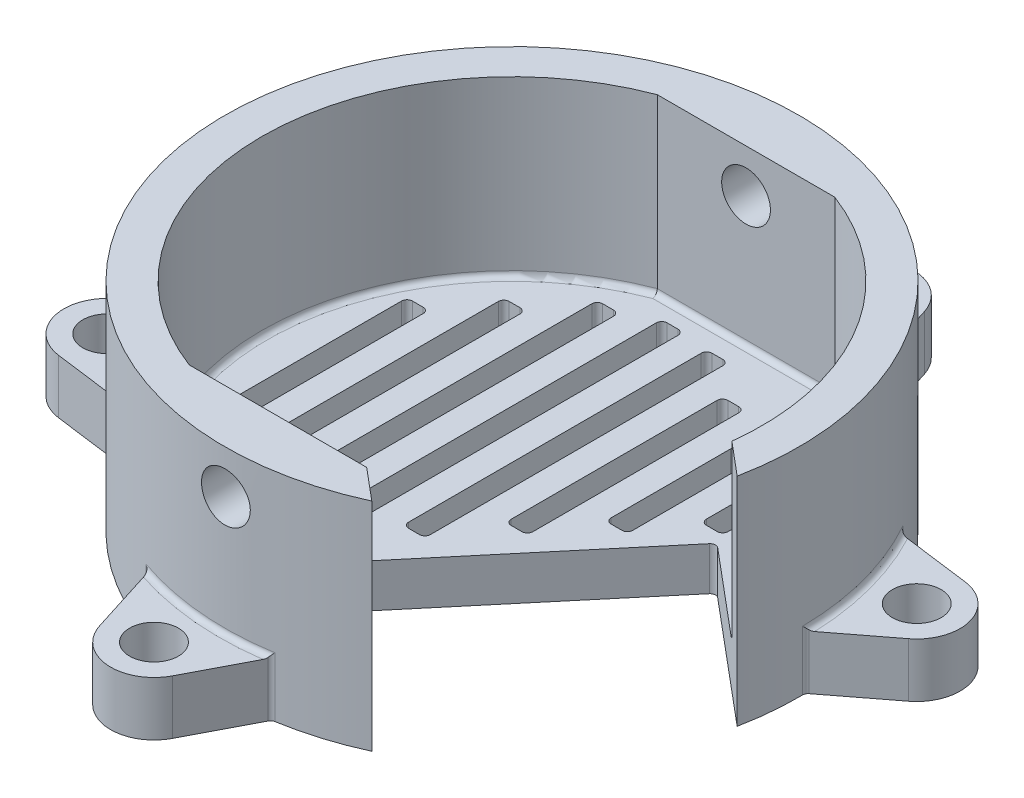
SolidWorks part; units mm, degrees
ref_plane "Front" through (0, 0, 0) normal (0, 0, 1) x (1, 0, 0)
ref_plane "Top" through (0, 0, 0) normal (0, 1, 0) x (1, 0, 0)
ref_plane "Right" through (0, 0, 0) normal (1, 0, 0) x (0, 0, -1)
sketch "Sketch1" plane through (0, 0, 0) normal (0, 1, 0) x (1, 0, 0)
  line L0 (-4.0942, 10.8) -> (4.0942, 10.8)
  line L1 (-4.0942, -10.8) -> (4.0942, -10.8)
  arc A0 (-4.0942, 10.8) -> (-4.0942, -10.8) centre (0, 0) ccw
  arc A1 (4.0942, -10.8) -> (4.0942, 10.8) centre (0, 0) ccw
  dimension "D1" = 23.1
  dimension "D2" = 10.8
  dimension "D3" = 10.8
extrude "Boss-Extrude1" add sketch "Sketch1" along normal blind 2
sketch "Sketch2" plane through (0, 0, 0) normal (0, 1, 0) x (1, 0, 0)
  line L2 (-4.0942, -10.8) -> (4.0942, -10.8)
  line L3 (4.0942, 10.8) -> (-4.0942, 10.8)
  line L4 (-4.0942, -10.8) -> (4.0942, -10.8)
  line L5 (4.0942, 10.8) -> (-4.0942, 10.8)
  circle A0 centre (0, 0) radius 13.25
  arc A3 (-4.0942, 10.8) -> (-4.0942, -10.8) centre (0, 0) ccw
  arc A4 (4.0942, -10.8) -> (4.0942, 10.8) centre (0, 0) ccw
  arc A5 (-4.0942, 10.8) -> (-4.0942, -10.8) centre (0, 0) ccw
  arc A6 (4.0942, -10.8) -> (4.0942, 10.8) centre (0, 0) ccw
  dimension "D1" = 26.5
  dimension "D2" = 0
extrude "Boss-Extrude2" add sketch "Sketch2" along normal blind 10
sketch "Sketch3" plane through (0, 2, 0) normal (0, 1, 0) x (1, 0, 0)
  line L0 (4.0942, -10.8) -> (-0.5021, -6.9433)
  line L1 (-0.5021, -6.9433) -> (7.2114, 2.2493)
  line L2 (7.2114, 2.2493) -> (11.4735, -1.3271)
  line L3 (4.4355, -12.6825) -> (13.8662, -1.4435) construction
  line L4 (3.3547, -2.347) -> (9.0782, -7.1496) construction
  line L5 (-4.0942, -10.8) -> (4.0942, -10.8) construction
  line L6 (4.0942, -10.8) -> (5.5577, -12.0281)
  line L7 (11.4735, -1.3271) -> (12.9921, -2.6014)
  arc A0 (4.0942, -10.8) -> (4.0942, 10.8) centre (0, 0) ccw construction
  circle A1 centre (0, 0) radius 13.25 construction
  arc A2 (12.9921, -2.6014) -> (5.5577, -12.0281) centre (0, 0) cw
  dimension "D1" = 12
  dimension "D2" = 40
  dimension "D3" = 6
extrude "Cut-Extrude1" cut sketch "Sketch3" along normal up to surface (8 mm away) up to face at (0, 10, 13.25)
extrude "Cut-Extrude3" cut sketch "Sketch3<3>" against normal up to surface (2 mm away) up to face at (0, 0, 13.25)
sketch "Sketch3<3>" plane through (0, 2, 0) normal (0, 1, 0) x (1, 0, 0) same geometry as "Sketch3"
sketch "Sketch4" plane through (0, 0, 0) normal (0, 0, 1) x (1, 0, 0)
  line L0 (0, 0) -> (0, 10) construction
  line L1 (-4.0942, 10) -> (4.0942, 10) construction
  circle A1 centre (0, 8) radius 1.125
  dimension "D1" = 2.25
  dimension "D2" = 2
extrude "Cut-Extrude4" cut sketch "Sketch4" against normal mid plane 30
sketch "Sketch5" plane through (0, 0, 0) normal (0, -1, 0) x (1, 0, 0)
  line L0 (0, 0) -> (1.1548, -13.1996) construction
  line L1 (0, 0) -> (0, -13.25) construction
  line L2 (3.2366, -15.7934) -> (4.2603, -12.5464)
  line L3 (-0.4449, -16.1155) -> (-2.0169, -13.0956)
  line L4 (0, 0) -> (11.4877, -13.6905) construction
  line L5 (-0.5021, 6.9433) -> (7.2114, -2.2493) construction
  line L6 (0, 0) -> (10.0176, 8.4058) construction
  line L7 (15.9479, -2.3603) -> (13.2469, -0.2877)
  line L8 (14.9914, -5.9299) -> (11.616, -6.3743)
  line L9 (-3.2366, 15.7934) -> (-4.2603, 12.5464)
  line L10 (0.4449, 16.1155) -> (2.0169, 13.0956)
  line L11 (-15.9479, 2.3603) -> (-13.2469, 0.2877)
  line L12 (-14.9914, 5.9299) -> (-11.616, 6.3743)
  arc A0 (5.5577, 12.0281) -> (12.9921, 2.6014) centre (0, 0) ccw construction
  circle A1 centre (1.3291, -15.192) radius 2 construction
  arc A2 (-0.4449, -16.1155) -> (3.2366, -15.7934) centre (1.3291, -15.192) ccw
  arc A3 (-2.0169, -13.0956) -> (4.2603, -12.5464) centre (0, 0) ccw
  arc A4 (5.5577, 12.0281) -> (12.9921, 2.6014) centre (0, 0) ccw construction
  circle A5 centre (1.3291, -15.192) radius 1.125
  circle A6 centre (14.7304, -3.947) radius 1.125
  arc A7 (15.9479, -2.3603) -> (14.9914, -5.9299) centre (14.7304, -3.947) cw
  arc A8 (13.2469, -0.2877) -> (11.616, -6.3743) centre (0, 0) cw
  arc A9 (0.4449, 16.1155) -> (-3.2366, 15.7934) centre (-1.3291, 15.192) ccw
  arc A10 (2.0169, 13.0956) -> (-4.2603, 12.5464) centre (0, 0) ccw
  circle A11 centre (-1.3291, 15.192) radius 1.125
  circle A12 centre (-14.7304, 3.947) radius 1.125
  arc A13 (-15.9479, 2.3603) -> (-14.9914, 5.9299) centre (-14.7304, 3.947) cw
  arc A14 (-13.2469, 0.2877) -> (-11.616, 6.3743) centre (0, 0) cw
  dimension "D2" = 4
  dimension "D3" = 45
  dimension "D4" = 2.25
  dimension "D1" = 5
extrude "Boss-Extrude4" add sketch "Sketch5" against normal blind 2.5
fillet "Fillet2" radius 0.25 18 edges at (-0.5021, 1, 6.9433) (7.2114, 1, -2.2493) (0, 2, 10.8) (9.8669, 2, -6.004) (-11.55, 2, 0) (0, 2, -10.8) (-1.1548, 2.5, 13.1996) (12.7985, 2.5, -3.4294) (1.1548, 2.5, -13.1996) (-12.7985, 2.5, 3.4294) (-2.0169, 1.25, -13.0956) (4.2603, 1.25, -12.5464) (11.616, 1.25, -6.3743) (13.2469, 1.25, -0.2877) (2.0169, 1.25, 13.0956) (-4.2603, 1.25, 12.5464) (-11.616, 1.25, 6.3743) (-13.2469, 1.25, 0.2877)
sketch "Sketch6" plane through (0, 0, 0) normal (0, -1, 0) x (1, 0, 0)
  line L1 (-9.75, 4.0968) -> (-8.75, 4.0968)
  line L2 (-9.75, 4.0968) -> (-9.75, -4.9032)
  line L3 (-9.75, -4.9032) -> (-8.75, -4.9032)
  line L4 (-8.75, 4.0968) -> (-8.75, -4.9032)
  line L5 (-7.5, 6.8805) -> (-6.5, 6.8805)
  line L6 (-7.5, 6.8805) -> (-7.5, -7.1195)
  line L7 (-7.5, -7.1195) -> (-6.5, -7.1195)
  line L8 (-6.5, 6.8805) -> (-6.5, -7.1195)
  line L9 (-5.25, 8.816) -> (-4.25, 8.816)
  line L10 (-5.25, 8.816) -> (-5.25, -9.184)
  line L11 (-5.25, -9.184) -> (-4.25, -9.184)
  line L12 (-4.25, 8.816) -> (-4.25, -9.184)
  line L13 (-3, 9.0929) -> (-2, 9.0929)
  line L14 (-3, 9.0929) -> (-3, -9.9071)
  line L15 (-3, -9.9071) -> (-2, -9.9071)
  line L16 (-2, 9.0929) -> (-2, -9.9071)
  line L17 (-0.75, 4.2695) -> (0.25, 4.2695)
  line L18 (-0.75, 4.2695) -> (-0.75, -9.7305)
  line L19 (-0.75, -9.7305) -> (0.25, -9.7305)
  line L20 (0.25, 4.2695) -> (0.25, -9.7305)
  line L21 (1.5, 1.7875) -> (2.5, 1.7875)
  line L22 (1.5, 1.7875) -> (1.5, -8.2125)
  line L23 (1.5, -8.2125) -> (2.5, -8.2125)
  line L24 (2.5, 1.7875) -> (2.5, -8.2125)
  line L25 (3.75, -0.573) -> (4.75, -0.573)
  line L26 (3.75, -0.573) -> (3.75, -6.573)
  line L27 (3.75, -6.573) -> (4.75, -6.573)
  line L28 (4.75, -0.573) -> (4.75, -6.573)
  line L29 (6, -2.7229) -> (7, -2.7229)
  line L30 (6, -2.7229) -> (6, -5.7229)
  line L31 (6, -5.7229) -> (7, -5.7229)
  line L32 (7, -2.7229) -> (7, -5.7229)
  dimension "D1" = 1
  dimension "D2" = 1.25
  dimension "D3" = 1.25
  dimension "D4" = 1.25
  dimension "D5" = 1.25
  dimension "D6" = 1.25
  dimension "D7" = 1.25
  dimension "D8" = 1.25
  dimension "D9" = 9
  dimension "D10" = 14
  dimension "D11" = 18
  dimension "D12" = 19
  dimension "D13" = 14
  dimension "D14" = 10
  dimension "D15" = 6
  dimension "D16" = 3
  dimension "D17" = 0.25
extrude "Cut-Extrude5" cut sketch "Sketch6" against normal up to surface (2 mm away) up to face at (2.1598, 2, 1.0622)
fillet "Fillet3" radius 0.25 32 edges at (-8.75, 1, 4.0968) (-6.5, 1, 6.8805) (-4.25, 1, 8.816) (-2, 1, 9.0929) (0.25, 1, 4.2695) (2.5, 1, 1.7875) (4.75, 1, -0.573) (7, 1, -2.7229) (-9.75, 1, 4.0968) (-7.5, 1, 6.8805) (-5.25, 1, 8.816) (-3, 1, 9.0929) (-0.75, 1, 4.2695) (1.5, 1, 1.7875) (3.75, 1, -0.573) (6, 1, -2.7229) (-6.5, 1, -7.1195) (-4.25, 1, -9.184) (-2, 1, -9.9071) (0.25, 1, -9.7305) (2.5, 1, -8.2125) (4.75, 1, -6.573) (7, 1, -5.7229) (-5.25, 1, -9.184) (-3, 1, -9.9071) (-0.75, 1, -9.7305) (1.5, 1, -8.2125) (3.75, 1, -6.573) (6, 1, -5.7229) (-7.5, 1, -7.1195) (-9.75, 1, -4.9032) (-8.75, 1, -4.9032)
